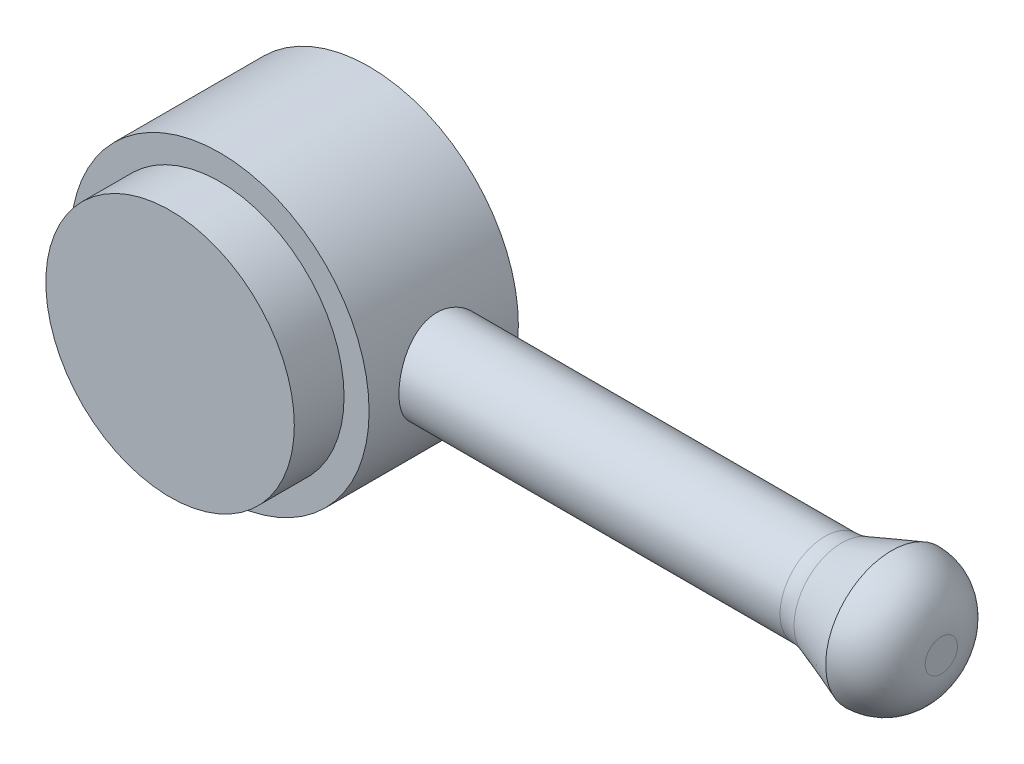
SolidWorks part; units mm, degrees
ref_plane "Front Plane" through (0, 0, 0) normal (0, 0, 1) x (1, 0, 0)
ref_plane "Top Plane" through (0, 0, 0) normal (0, 1, 0) x (1, 0, 0)
ref_plane "Right Plane" through (0, 0, 0) normal (1, 0, 0) x (0, 0, -1)
sketch "Sketch1" plane through (0, 0, 0) normal (0, 0, 1) x (1, 0, 0)
  circle A0 centre (0, 0) radius 12.485
  dimension "D1" = 24.97
extrude "Boss-Extrude1" add sketch "Sketch1" along normal blind 20
sketch "Sketch2" plane through (0, 0, 0) normal (0, 0, -1) x (-1, 0, 0)
  circle A1 centre (0, 0) radius 15
  dimension "D1" = 30
extrude "Boss-Extrude2" add sketch "Sketch2" along normal blind 15
sketch "Sketch3" plane through (0, 0, 0) normal (1, 0, 0) x (0, 0, -1)
  circle A0 centre (7.5, 0) radius 4.5
  dimension "D1" = 9
extrude "Boss-Extrude3" add sketch "Sketch3" along normal blind 55
sketch "Sketch4" plane through (55, 0, 0) normal (1, 0, 0) x (0, 0, -1)
  circle A3 centre (7.5, 0) radius 4.8
  circle A4 centre (7.5, 0) radius 4.8
  dimension "D1" = 0.3
extrude "Boss-Extrude4" add sketch "Sketch4" along normal blind 5 draft 20 draft outward yes
sketch "Sketch5" plane through (60, 0, 0) normal (1, 0, 0) x (0, 0, -1)
  circle A2 centre (7.5, 0) radius 6.6199
  circle A3 centre (7.5, 0) radius 6.6199
  dimension "D1" = 0
extrude "Boss-Extrude6" add sketch "Sketch5" along normal blind 5
fillet "Fillet1" radius 5 1 edges at (65, 0, -14.1199)
fillet "Fillet2" radius 5 1 edges at (55, 0, -12)
sketch "Sketch6" plane through (0, 0, 20) normal (0, 0, 1) x (1, 0, 0)
  circle A2 centre (0, 0) radius 12.485
  circle A3 centre (0, 0) radius 12.485
  dimension "D1" = 0
extrude "Cut-Extrude2" cut sketch "Sketch6" against normal blind 15
